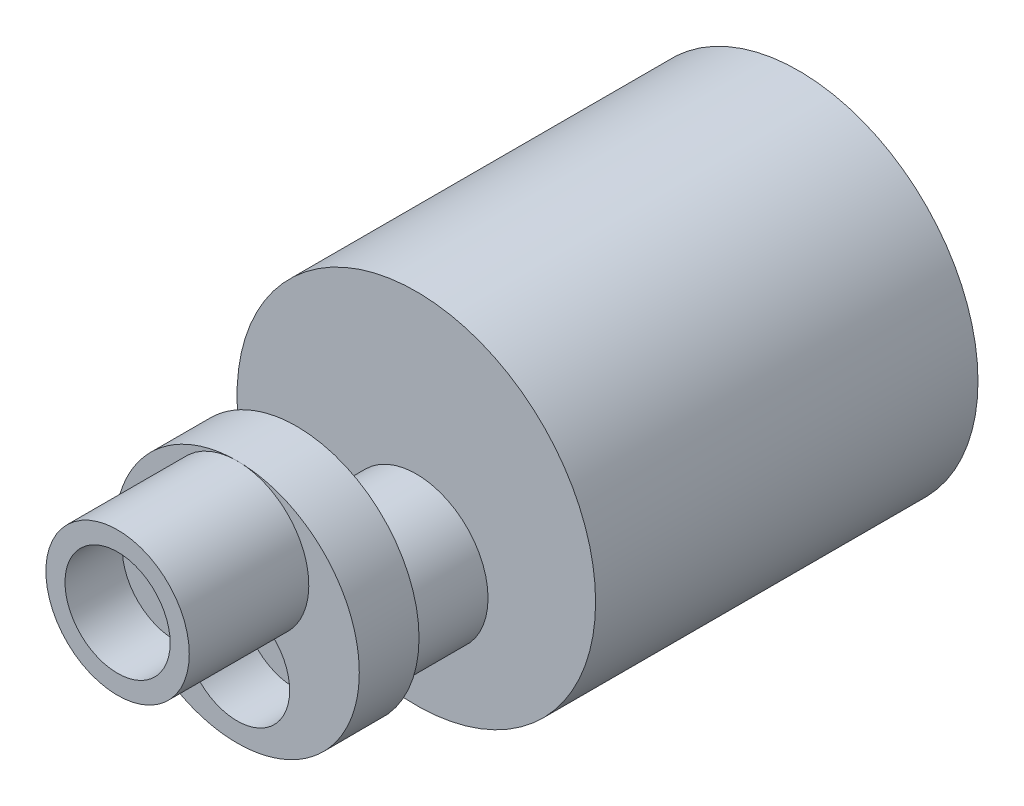
SolidWorks part; units mm, degrees
ref_plane "Front Plane" through (0, 0, 0) normal (0, 0, 1) x (1, 0, 0)
ref_plane "Top Plane" through (0, 0, 0) normal (0, 1, 0) x (1, 0, 0)
ref_plane "Right Plane" through (0, 0, 0) normal (1, 0, 0) x (0, 0, -1)
sketch "Sketch1" plane through (0, 0, 0) normal (0, 0, 1) x (1, 0, 0)
  circle A0 centre (0, 0) radius 7.5
  dimension "D1" = 15
extrude "Boss-Extrude1" add sketch "Sketch1" along normal blind 16
sketch "Sketch2" plane through (0, 0, 16) normal (0, 0, 1) x (1, 0, 0)
  circle A0 centre (0, -2.1125) radius 3
  dimension "D2" = 6
  dimension "D1" = 2.1125
extrude "Boss-Extrude2" add sketch "Sketch2" along normal blind 5
sketch "Sketch3" plane through (0, 0, 21) normal (0, 0, 1) x (1, 0, 0)
  circle A0 centre (0, 0) radius 5.1125
  dimension "D1" = 10.225
extrude "Boss-Extrude3" add sketch "Sketch3" along normal blind 2.5 contours A0
sketch "Sketch5" plane through (0, 0, 23.5) normal (0, 0, 1) x (1, 0, 0)
  circle A0 centre (0, 2.1125) radius 3
  dimension "D1" = 6
  dimension "D2" = 2.1125
extrude "Boss-Extrude4" add sketch "Sketch5" along normal blind 5
hole_wizard "CBORE for M2 Hex Socket Head Cap Screw1" positions "Sketch6" profile "Sketch8" counterbore size "M2" standard "ISO" end condition up to next
sketch "Sketch6" plane through (0, 0, 28.5) normal (0, 0, 1) x (1, 0, 0)
  circle A2 centre (0, 2.1125) radius 3
  circle A3 centre (0, 2.1125) radius 3
  point P5 (0, 2.1125)
  dimension "D1" = 0
sketch "Sketch8" plane through (0, 2.1125, 28.5) normal (1, 0, 0) x (0, -1, 0)
  line L0 (0, 0) -> (0, 7.5)
  line L1 (0, 7.5) -> (1.2, 7.5)
  line L3 (1.2, 7.5) -> (1.2, 2.4)
  line L4 (1.2, 2.4) -> (2.2, 2.4)
  line L5 (2.2, 2.4) -> (2.2, 0)
  line L7 (2.2, 0) -> (0, 0)
  line L11 (0, -6.35) -> (0, 107.95) construction
  dimension "Thru Hole Dia." = 2.4
  dimension "Thru Hole Depth" = 7.5
  dimension "C'Bore Dia." = 4.4
  dimension "C'Bore Depth" = 2.4
hole_wizard "CBORE for M2 Hex Socket Head Cap Screw2" positions "Sketch12" profile "Sketch10" counterbore size "M2" standard "ISO"
sketch "Sketch12" plane through (0, 0, 23.5) normal (0, 0, 1) x (1, 0, 0)
  circle A0 centre (0, -2.1125) radius 3 construction
  circle A1 centre (0, -2.1125) radius 3
  point P0 (0, -2.1125)
sketch "Sketch10" plane through (0, -2.1125, 23.5) normal (1, 0, 0) x (0, -1, 0)
  line L0 (0, 0) -> (0, 14.721)
  line L1 (0, 14.721) -> (1.2, 14)
  line L2 (1.2, 14) -> (1.2, 2.4)
  line L3 (1.2, 2.4) -> (2.2, 2.4)
  line L4 (2.2, 2.4) -> (2.2, 0)
  line L5 (2.2, 0) -> (0, 0)
  line L10 (0, 14.721) -> (-1.2, 14) construction
  line L11 (0, -6.35) -> (0, 107.95) construction
  dimension "Hole Dia." = 2.4
  dimension "Hole Depth" = 14
  dimension "C'Bore Dia." = 4.4
  dimension "C'Bore Depth" = 2.4
  dimension "Drill Angle" = 118
equation "\"roller_radius\"= 6.5"
equation "\"eccentricity\"= \"roller_radius\" * 0.325"
equation "\"outer_radius\"= 40"
equation "\"eccentric_shaft_radius\"= 16"
equation "\"rotor_width\"= 10"
equation "\"housing_depth\"= 40"
equation "\"bottom_depth\"= 5"
equation "\"roller_bearing_OD\"= \"roller_radius\" * 2"
equation "\"roller_bearing_ID\"= 6"
equation "\"eccentric_bearing_ID\"= 6"
equation "\"eccentric_bearing_OD\"= 15"
equation "\"roller_bearing_height\"= 5"
equation "\"eccentric_bearing_height\"= 5"
equation "\"bottom_bearing_ID\"= 15"
equation "\"bottom_bearing_OD\"= 32"
equation "\"bottom_bearing_height\"= 9"
equation "\"distance_to_output_rotor_holes\"= 20"
equation "\"D1@Sketch1\"=\"bottom_bearing_ID\""
equation "\"D1@Boss-Extrude1\"=\"bottom_bearing_height\"+7"
equation "\"D1@Sketch2\"=\"eccentricity\""
equation "\"D2@Sketch2\"=\"eccentric_bearing_ID\""
equation "\"D1@Boss-Extrude2\"=\"eccentric_bearing_height\""
equation "\"D1@Sketch5\"=\"eccentric_bearing_ID\""
equation "\"D2@Sketch5\"=\"eccentricity\""
equation "\"D1@Boss-Extrude4\"=\"eccentric_bearing_height\""
equation "\"output_bearing_ID\" = 25"
equation "\"output_bearing_OD\" = 37"
equation "\"output_bearing_height\" = 7"
equation "\"number_of_rollers\" = 15"
equation "\"housing_height\" = 27"
equation "\"spacer_1\" = 7"
equation "\"spacer_2\" = 2.5"
equation "\"spacer_3\" = 7.5"
equation "\"roller_pin_depth\" = 5"
equation "\"D1@Boss-Extrude3\"=\"spacer_2\""
